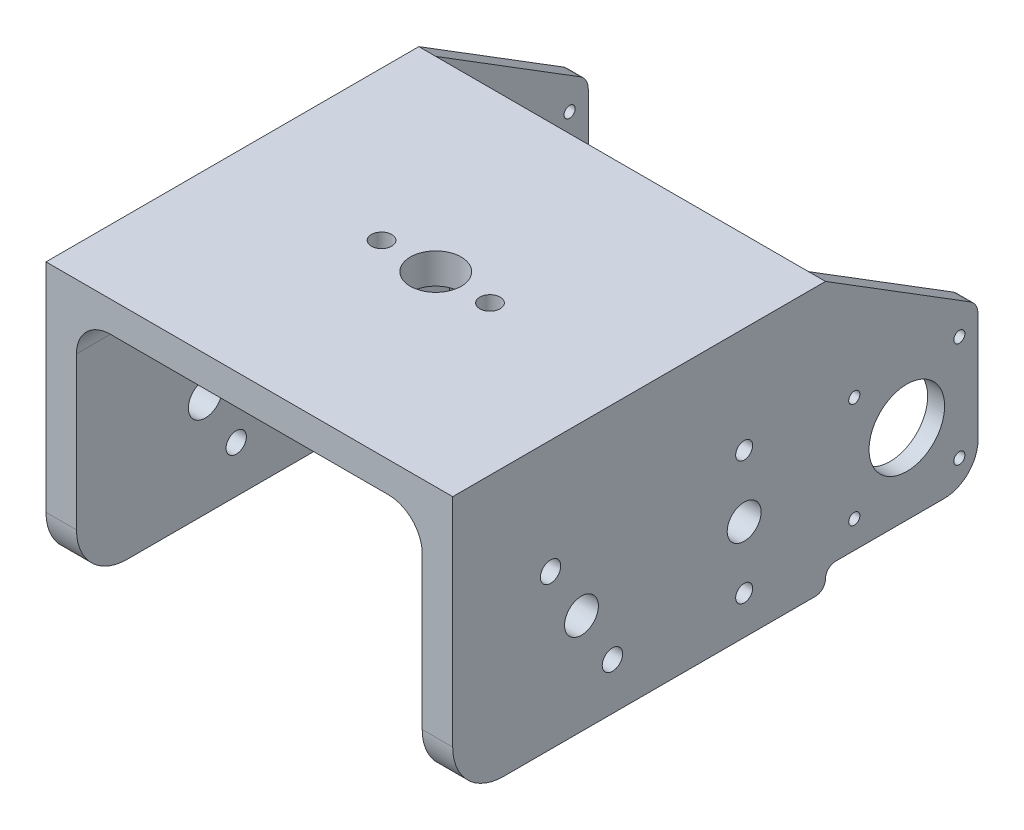
SolidWorks part; units mm, degrees
ref_plane "Ön Düzlem" through (0, 0, 0) normal (0, 0, 1) x (1, 0, 0)
ref_plane "Üst Düzlem" through (0, 0, 0) normal (0, 1, 0) x (1, 0, 0)
ref_plane "Sağ Düzlem" through (0, 0, 0) normal (1, 0, 0) x (0, 0, -1)
sketch "Sketch1" plane through (0, 0, 0) normal (0, 1, 0) x (1, 0, 0)
  line L1 (-60, 55) -> (60, 55)
  line L2 (-60, 55) -> (-60, -55)
  line L3 (-60, -55) -> (60, -55)
  line L4 (60, 55) -> (60, -55)
  line L5 (-60, 55) -> (60, -55) construction
  line L6 (-60, -55) -> (60, 55) construction
  point P0 (0, 0)
  dimension "D1" = 110
  dimension "D2" = 120
extrude "Boss-Extrude1" add sketch "Sketch1" along normal blind 9
sketch "Sketch2" plane through (0, 0, 0) normal (0, -1, 0) x (1, 0, 0)
  line L0 (-60, 55) -> (60, 55) construction
  line L1 (-60, -55) -> (-51, -55)
  line L2 (-60, -55) -> (-60, 55)
  line L3 (-60, 55) -> (-51, 55)
  line L4 (-51, -55) -> (-51, 55)
  line L6 (60, -55) -> (51, -55)
  line L7 (60, -55) -> (60, 55)
  line L8 (60, 55) -> (51, 55)
  line L9 (51, -55) -> (51, 55)
  dimension "D1" = 9
  dimension "D2" = 9
extrude "Boss-Extrude2" add sketch "Sketch2" along normal blind 70
sketch "Sketch3" plane through (0, 0, 0) normal (0, -1, 0) x (1, 0, 0)
  circle A0 centre (0, 0) radius 7.5
  dimension "D1" = 15
extrude "Cut-Extrude1" cut sketch "Sketch3" against normal blind 70
sketch "Sketch4" plane through (-60, 0, 0) normal (-1, 0, 0) x (0, 0, 1)
  line L0 (-31, -22.149) -> (-31, -58.649) construction
  line L1 (-55, 9) -> (-55, -70) construction
  line L3 (55, -70) -> (-55, -70) construction
  line L6 (7.875, -56.2039) -> (26.125, -24.594) construction
  line L7 (-55, 9) -> (55, 9) construction
  line L8 (55, 9) -> (55, -70) construction
  circle A5 centre (7.875, -56.2039) radius 3
  circle A6 centre (26.125, -24.594) radius 3
  circle A7 centre (17, -40.399) radius 5
  circle A8 centre (-31, -22.149) radius 2.5
  circle A9 centre (-31, -58.649) radius 2.5
  circle A10 centre (-31, -40.399) radius 5
  dimension "D5" = 5
  dimension "D6" = 5
  dimension "D7" = 24
  dimension "D10" = 6
  dimension "D11" = 6
  dimension "D12" = 10
  dimension "D8" = 49.399
  dimension "D9" = 10
  dimension "D14" = 29.601
  dimension "D17" = 18.25
  dimension "D2" = 48
  dimension "D3" = 0
  dimension "D4" = 36.5
  dimension "D13" = 38
  dimension "D15" = 30
  dimension "D16" = 36.5
extrude "Cut-Extrude2" cut sketch "Sketch4" against normal through all
fillet "Fillet1" radius 10 2 edges at (51, 0, 0) (-51, 0, 0)
sketch "Sketch6" plane through (0, 9, 0) normal (0, 1, 0) x (1, 0, 0)
  line L0 (-16, 0) -> (16, 0) construction
  circle A0 centre (-16, 0) radius 3
  circle A1 centre (16, 0) radius 3
  point P5 (0, 0)
  dimension "D2" = 6
  dimension "D3" = 6
  dimension "D1" = 32
extrude "Cut-Extrude4" cut sketch "Sketch6" against normal blind 10
fillet "Fillet2" radius 15 2 edges at (55.5, -70, 55) (-55.5, -70, 55)
sketch "Sketch7" plane through (60, 0, 0) normal (1, 0, 0) x (0, 0, -1)
  line L0 (55, 9) -> (55, -70) construction
  line L1 (55, -19) -> (100, -19)
  line L2 (55, -19) -> (55, -64)
  line L3 (55, -64) -> (100, -64)
  line L4 (100, -19) -> (100, -64)
  line L5 (55, -70) -> (-40, -70) construction
  line L6 (63.5, -24.899) -> (63.5, -55.899) construction
  line L7 (63.5, -55.899) -> (94.5, -55.899) construction
  line L8 (94.5, -55.899) -> (94.5, -24.899) construction
  line L9 (94.5, -24.899) -> (63.5, -24.899) construction
  circle A0 centre (63.5, -24.899) radius 1.65
  circle A1 centre (94.5, -24.899) radius 1.65
  circle A2 centre (94.5, -55.899) radius 1.65
  circle A3 centre (63.5, -55.899) radius 1.65
  circle A4 centre (79, -40.399) radius 11.15
  circle A5 centre (31, -40.399) radius 5 construction
  point P12 (79, -24.899)
  point P14 (63.5, -40.399)
  dimension "D8" = 22.3
  dimension "D11" = 3.3
  dimension "D12" = 3.3
  dimension "D13" = 3.3
  dimension "D14" = 3.3
  dimension "D1" = 45
  dimension "D2" = 45
  dimension "D3" = 6
  dimension "D4" = 31
  dimension "D5" = 31
  dimension "D6" = 48
  dimension "D7" = 0
  dimension "D9" = 0
  dimension "D10" = 0
extrude "Boss-Extrude3" add sketch "Sketch7" against normal blind 5
sketch "Sketch8" plane through (-60, 0, 0) normal (-1, 0, 0) x (0, 0, 1)
  line L0 (-55, 9) -> (-55, -70) construction
  line L1 (-55, -19) -> (-100, -19)
  line L2 (-55, -19) -> (-55, -64)
  line L3 (-55, -64) -> (-100, -64)
  line L4 (-100, -19) -> (-100, -64)
  line L6 (40, -70) -> (-55, -70) construction
  line L7 (-94.5, -24.899) -> (-63.5, -24.899) construction
  line L8 (-63.5, -24.899) -> (-63.5, -55.899) construction
  line L9 (-63.5, -55.899) -> (-94.5, -55.899) construction
  line L10 (-94.5, -55.899) -> (-94.5, -24.899) construction
  circle A0 centre (-31, -40.399) radius 5 construction
  circle A1 centre (-94.5, -24.899) radius 1.65
  circle A2 centre (-63.5, -24.899) radius 1.65
  circle A3 centre (-94.5, -55.899) radius 1.65
  circle A4 centre (-63.5, -55.899) radius 1.65
  circle A5 centre (-79, -40.399) radius 11.15
  point P10 (-79, -24.899)
  point P17 (-63.5, -40.399)
  dimension "D4" = 31
  dimension "D7" = 0
  dimension "D8" = 3.3
  dimension "D9" = 3.3
  dimension "D10" = 3.3
  dimension "D11" = 3.3
  dimension "D14" = 22.3
  dimension "D1" = 45
  dimension "D2" = 45
  dimension "D3" = 6
  dimension "D5" = 31
  dimension "D6" = 48
  dimension "D12" = 0
  dimension "D13" = 0
extrude "Boss-Extrude4" add sketch "Sketch8" against normal blind 5
fillet "Fillet3" radius 15 2 edges at (57.5, -19, -55) (-57.5, -19, -55)
fillet "Fillet5" radius 3 4 edges at (-57.5, -64, -55) (-55.5, -70, -55) (55.5, -70, -55) (57.5, -64, -55)
sketch "Sketch10" plane through (60, 0, 0) normal (1, 0, 0) x (0, 0, -1)
  line L0 (55, 9) -> (100, -19)
  line L1 (100, -19) -> (90.5558, -19)
  line L2 (100, -19) -> (70, -19) construction
  line L3 (90.5558, -19) -> (55, 3.1236)
  line L4 (55, 9) -> (55, -4) construction
  line L5 (55, 3.1236) -> (55, 9)
extrude "Boss-Extrude5" add sketch "Sketch10" against normal up to vertex (120 mm away) up to point (-60, -19, -70)
sketch "Sketch11" plane through (0, 0, 0) normal (0, -1, 0) x (-1, 0, 0)
  line L1 (55, 55) -> (-55, 55)
  line L2 (55, 55) -> (55, 100)
  line L3 (55, 100) -> (-55, 100)
  line L4 (-55, 55) -> (-55, 100)
extrude "Cut-Extrude5" cut sketch "Sketch11" against normal blind 10 and the other way blind 51
fillet "Fillet6" radius 5 6 edges at (-57.5, -19, -100) (-57.5, 3.1236, -55) (-57.5, -19, -90.5558) (57.5, -19, -90.5558) (57.5, -19, -100) (57.5, 3.1236, -55)
fillet "Fillet7" radius 10 2 edges at (57.5, -64, -100) (-57.5, -64, -100)
sketch "Sketch12" plane through (-60, 0, 0) normal (-1, 0, 0) x (0, 0, 1)
  line L0 (-58.9407, 2.767) -> (-81.4993, -11.6936)
  line L1 (-81.4993, -11.6936) -> (-78.6071, -21.1412)
  line L2 (-78.6071, -21.1412) -> (-64.5322, -21.1412)
  line L3 (-64.5322, -21.1412) -> (-49.3551, -12.1865)
  line L4 (-49.3551, -12.1865) -> (-49.3551, -1.8535)
  line L5 (-49.3551, -1.8535) -> (-58.9407, 2.767)
extrude "Boss-Extrude6" add sketch "Sketch12" against normal up to vertex
sketch "Sketch13" plane through (60, 0, 0) normal (1, 0, 0) x (0, 0, -1)
  line L0 (56.8198, 2.8852) -> (82.4633, -10.4185)
  line L1 (82.4633, -10.4185) -> (80.9208, -18.9021)
  line L2 (80.9208, -18.9021) -> (69.6416, -22.3726)
  line L3 (69.6416, -22.3726) -> (52.5781, -14.6603)
  line L4 (52.5781, -14.6603) -> (45.0585, -6.5624)
  line L5 (45.0585, -6.5624) -> (48.8183, 0.6847)
  line L6 (48.8183, 0.6847) -> (56.8198, 0.6847)
  line L7 (56.8198, 0.6847) -> (56.8198, 2.8852)
extrude "Boss-Extrude7" add sketch "Sketch13" against normal up to vertex
equation "\"0o\"=1.26614"
